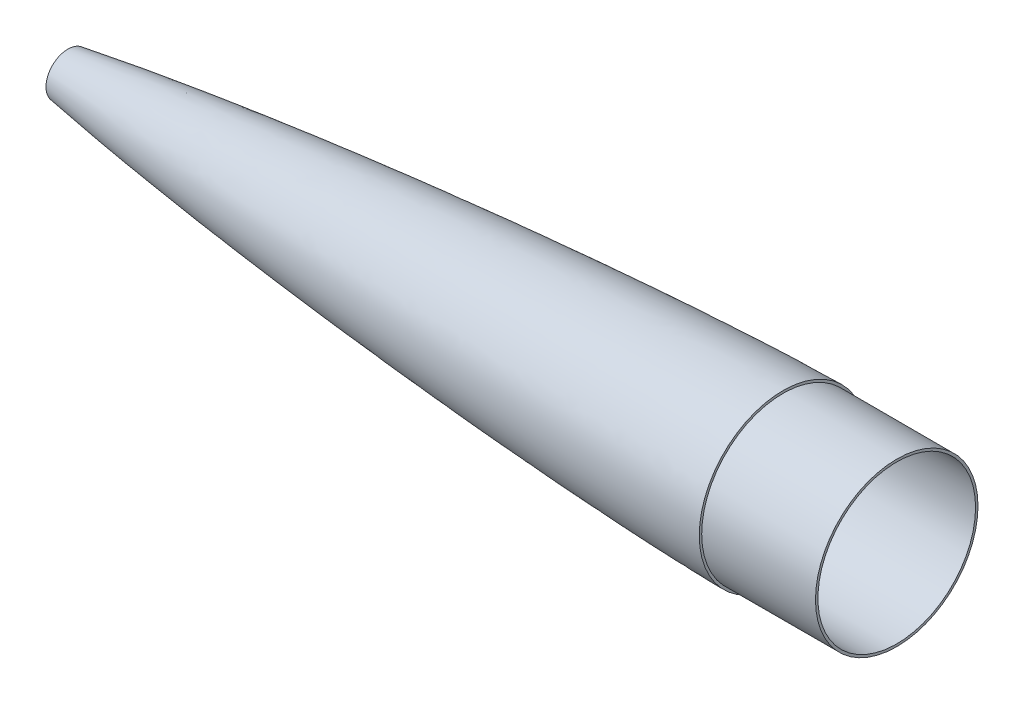
SolidWorks part; units mm, degrees
ref_plane "Front Plane" through (0, 0, 0) normal (0, 0, 1) x (1, 0, 0)
ref_plane "Top Plane" through (0, 0, 0) normal (0, 1, 0) x (1, 0, 0)
ref_plane "Right Plane" through (0, 0, 0) normal (1, 0, 0) x (0, 0, -1)
sketch "Sketch1" plane through (0, 0, 0) normal (0, 1, 0) x (1, 0, 0)
  line L0 (0, 0) -> (635, 0)
  line L1 (635, 0) -> (635, 65.405)
  spline S0 degree 4 poles (0, 0) (0.0022, 0.0063) (0.0075, 0.0184) (0.0223, 0.0404) (0.057, 0.0804) (0.1098, 0.1304) (0.1816, 0.1889) (0.2836, 0.2634) (0.4063, 0.3444) (0.5502, 0.4318) (0.7155, 0.5251) (0.9567, 0.6537) (1.3318, 0.8391) (1.9703, 1.1275) (3.1158, 1.5922) (5.1634, 2.3284) (8.9332, 3.5155) (16.022, 5.4463) (28.2617, 8.305) (49.1788, 12.5136) (77.9573, 17.4873) (112.8708, 22.8061) (151.8575, 28.1242) (190.9036, 32.9827) (229.9952, 37.4592) (269.1232, 41.6038) (308.2821, 45.4454) (347.4678, 49.0026) (386.6776, 52.2836) (425.9094, 55.2895) (465.1619, 58.0128) (504.4341, 60.4362) (538.8141, 62.2665) (568.2945, 63.5925) (591.9899, 64.4666) (607.8766, 64.942) (620.8678, 65.2384) (628.9431, 65.3608) (632.981, 65.3999) (635, 65.405) knots 0 0 0 0 0 0.000041 0.000083 0.000165 0.000331 0.000496 0.000661 0.000955 0.001249 0.001549 0.001849 0.002664 0.003866 0.00593 0.009578 0.01627 0.028579 0.051871 0.088176 0.149698 0.211221 0.272743 0.334265 0.395788 0.45731 0.518832 0.580355 0.641877 0.703399 0.764922 0.826444 0.887966 0.918727 0.949489 0.974744 0.987372 1 1 1 1 1 construction
  spline S1 degree 4 poles (0, 0) (0.0022, 0.0063) (0.0075, 0.0184) (0.0223, 0.0404) (0.057, 0.0804) (0.1098, 0.1304) (0.1816, 0.1889) (0.2836, 0.2634) (0.4063, 0.3444) (0.5502, 0.4318) (0.7155, 0.5251) (0.9567, 0.6537) (1.3318, 0.8391) (1.9703, 1.1275) (3.1158, 1.5922) (5.1634, 2.3284) (8.9332, 3.5155) (16.022, 5.4463) (28.2617, 8.305) (49.1788, 12.5136) (77.9573, 17.4873) (112.8708, 22.8061) (151.8575, 28.1242) (190.9036, 32.9827) (229.9952, 37.4592) (269.1232, 41.6038) (308.2821, 45.4454) (347.4678, 49.0026) (386.6776, 52.2836) (425.9094, 55.2895) (465.1619, 58.0128) (504.4341, 60.4362) (538.8141, 62.2665) (568.2945, 63.5925) (591.9899, 64.4666) (607.8766, 64.942) (620.8678, 65.2384) (628.9431, 65.3608) (632.981, 65.3999) (635, 65.405) knots 0 0 0 0 0 0.000041 0.000083 0.000165 0.000331 0.000496 0.000661 0.000955 0.001249 0.001549 0.001849 0.002664 0.003866 0.00593 0.009578 0.01627 0.028579 0.051871 0.088176 0.149698 0.211221 0.272743 0.334265 0.395788 0.45731 0.518832 0.580355 0.641877 0.703399 0.764922 0.826444 0.887966 0.918727 0.949489 0.974744 0.987372 1 1 1 1 1
  dimension "D1" = 65.405
revolve "Revolve1" add sketch "Sketch1" angle 360 about L0
shell "Shell1" thickness 3.81 removed face at (635, 0, 65.405)
sketch "Sketch2" plane through (635, 0, 0) normal (1, 0, 0) x (0, 0, -1)
  circle A0 centre (0, 0) radius 61.595
  circle A1 centre (0, 0) radius 63.5
  dimension "D1" = 127
  dimension "D2" = 123.19
extrude "Boss-Extrude1" add sketch "Sketch2" along normal blind 88.9
ref_plane "Plane1" through (0, 0, -203.2) normal (0, 0, 1) x (1, 0, 0)
sketch "Sketch3" plane through (0, 0, -203.2) normal (0, 0, 1) x (1, 0, 0)
  line L1 (0, 63.5) -> (76.2, 63.5)
  line L2 (0, 63.5) -> (0, -63.5)
  line L3 (0, -63.5) -> (76.2, -63.5)
  line L4 (76.2, 63.5) -> (76.2, -63.5)
  point P4 (0, 0)
  dimension "D1" = 127
  dimension "D2" = 76.2
extrude "Cut-Extrude4" cut sketch "Sketch3" along normal blind 572.262 contours L2 L1 L4 L3
